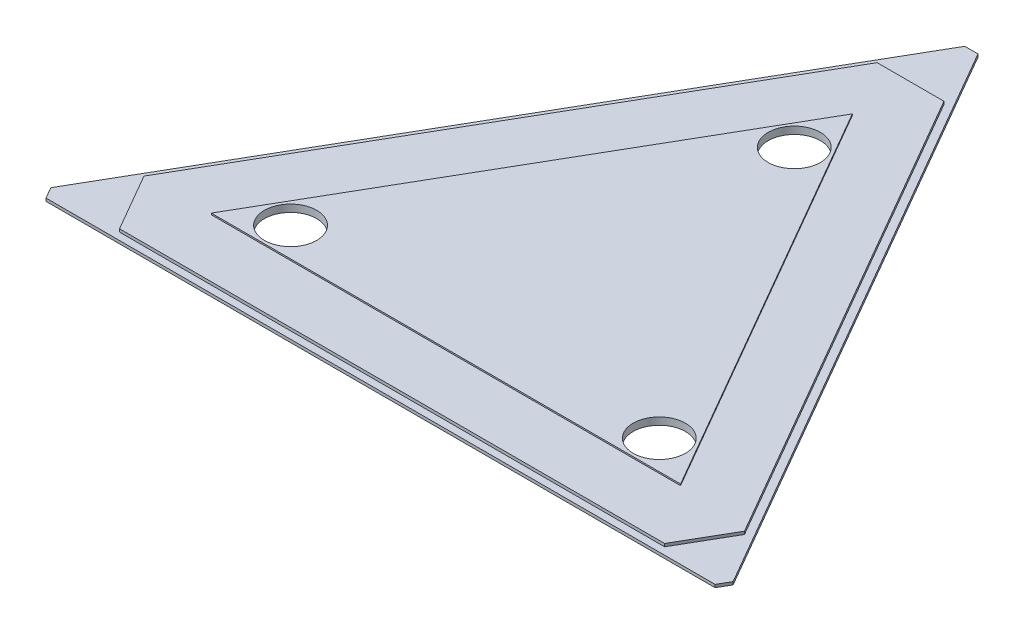
SolidWorks part; units mm, degrees
ref_plane "Front Plane" through (0, 0, 0) normal (0, 0, 1) x (1, 0, 0)
ref_plane "Top Plane" through (0, 0, 0) normal (0, 1, 0) x (1, 0, 0)
ref_plane "Right Plane" through (0, 0, 0) normal (1, 0, 0) x (0, 0, -1)
sketch "Sketch1" plane through (0, 0, 0) normal (0, 1, 0) x (1, 0, 0)
  line L1 (347.2736, 23.6092) -> (347.2736, 3.6092) construction
  line L2 (428.1137, -116.4172) -> (410.7932, -106.4172) construction
  line L8 (243.3042, -116.4848) -> (254.8093, -136.4089)
  line L10 (266.4391, -116.428) -> (283.7585, -106.4261) construction
  line L13 (452.6999, -118.9847) -> (442.6021, -136.4093)
  line L19 (231.9812, -138.9144) -> (229.7127, -134.9863)
  line L21 (344.9807, 64.6634) -> (229.7127, -134.9863)
  line L22 (349.5168, 64.6634) -> (344.9807, 64.6634)
  line L27 (464.7848, -134.9867) -> (462.5171, -138.9144)
  line L28 (462.5171, -138.9144) -> (231.9812, -138.9144)
  line L35 (335.7675, 43.666) -> (243.3042, -116.4848)
  line L36 (358.7782, 43.666) -> (335.7675, 43.666)
  line L57 (266.4391, -116.428) -> (428.1137, -116.4172)
  line L58 (347.2736, 23.6092) -> (428.1137, -116.4172)
  line L59 (266.4391, -116.428) -> (347.2736, 23.6092)
  line L62 (452.6999, -118.9847) -> (358.7782, 43.666)
  line L63 (442.6021, -136.4093) -> (254.8093, -136.4089)
  line L69 (464.7848, -134.9867) -> (349.5168, 64.6634)
  circle A1 centre (347.2736, 3.6092) radius 1.5
  circle A2 centre (283.7585, -106.4261) radius 1.5
  circle A3 centre (410.7932, -106.4172) radius 1.5
  circle A4 centre (347.2736, 3.6092) radius 7.5
  circle A5 centre (410.7932, -106.4172) radius 7.5
  circle A6 centre (283.7585, -106.4261) radius 7.5
  circle A7 centre (347.2736, 3.6092) radius 9
  circle A8 centre (410.7932, -106.4172) radius 9
  circle A9 centre (283.7585, -106.4261) radius 9
  dimension "D1" = 20
  dimension "D2" = 3
  dimension "D5" = 3
  dimension "D6" = 3
  dimension "D7" = 15
  dimension "D8" = 15
  dimension "D9" = 15
  dimension "D10" = 18
  dimension "D11" = 18
  dimension "D12" = 18
  dimension "D3" = 20
  dimension "D4" = 20
extrude "Boss-Extrude1" add sketch "Sketch1" along normal blind 1 contours L27 L69 L22 L21 L19 L28 L13 L63 L8 L35 L36 L62 region at (233.5399, 0, 135.3952)
extrude "Boss-Extrude2" add sketch "Sketch1<12>" along normal blind 2 contours L63 L13 L62 L36 L35 L8 L57 L59 L58 region at (291.9276, 0, 37.7903)
sketch "Sketch1<12>" plane through (0, 0, 0) normal (0, 1, 0) x (1, 0, 0) same geometry as "Sketch1"
extrude "Boss-Extrude3" add sketch "Sketch1<13>" along normal blind 2.5 contours L59 L57 L58 region at (347.2755, 0, 69.7454)
sketch "Sketch1<13>" plane through (0, 0, 0) normal (0, 1, 0) x (1, 0, 0) same geometry as "Sketch1"
